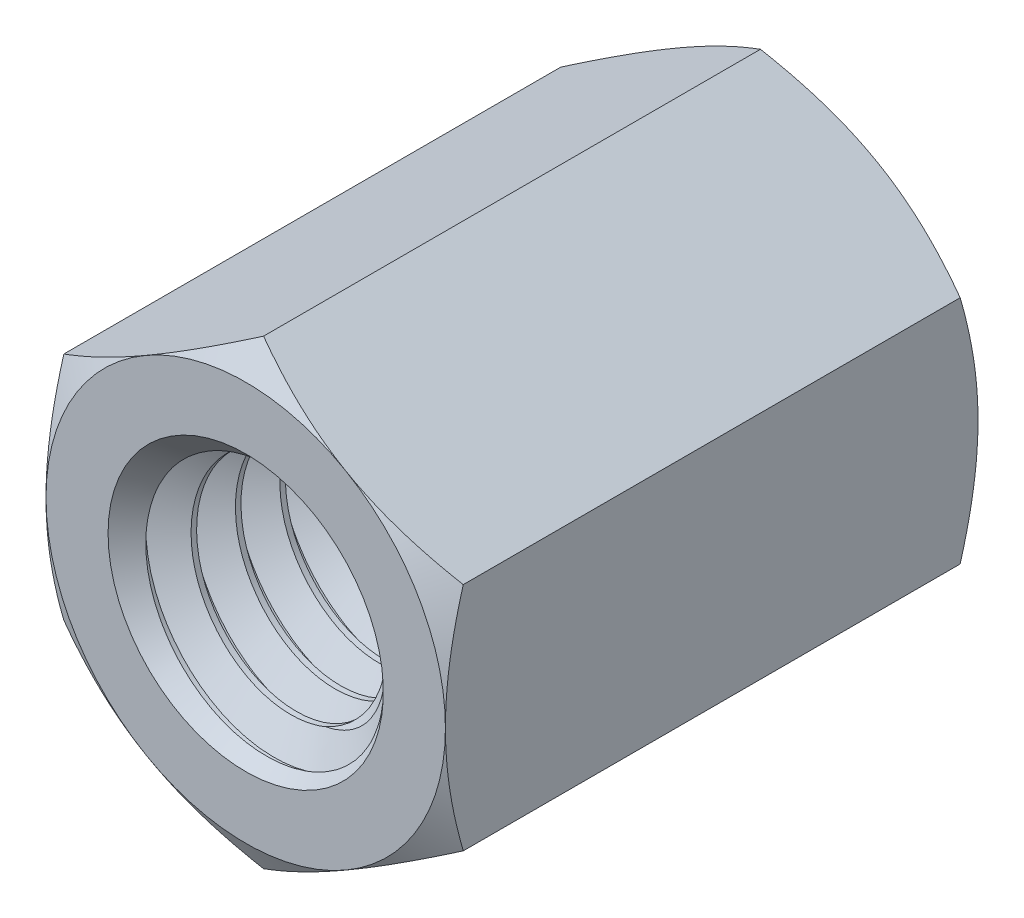
SolidWorks part; units mm, degrees
material "Brass"
ref_plane "Front Plane" through (0, 0, 0) normal (0, 0, 1) x (1, 0, 0)
ref_plane "Top Plane" through (0, 0, 0) normal (0, 1, 0) x (1, 0, 0)
ref_plane "Right Plane" through (0, 0, 0) normal (1, 0, 0) x (0, 0, -1)
sketch "Sketch3" plane through (0, 0, 0) normal (1, 0, 0) x (0, 0, -1)
  line L0 (-3, 0) -> (3, 0) construction
  line L1 (0, 2.25) -> (0, -2.25) construction
  line L2 (-3, 1.5) -> (-3, -1.5) construction
  point P2 (-1.8, 0)
  point P3 (1.8, 0)
  dimension "Length" = 6
  dimension "Min Thread Length" = 4.8
  dimension "D1" = 4.8
  dimension "Thread Dia" = 3
  dimension "Hex" = 4.5
sketch "Sketch1" plane through (0, 0, 0) normal (0, 0, 1) x (1, 0, 0)
  line L1 (0, 2.5981) -> (-2.25, 1.299)
  line L2 (-2.25, 1.299) -> (-2.25, -1.299)
  line L3 (-2.25, -1.299) -> (0, -2.5981)
  line L4 (0, -2.5981) -> (2.25, -1.299)
  line L5 (2.25, -1.299) -> (2.25, 1.299)
  line L6 (2.25, 1.299) -> (0, 2.5981)
  circle A0 centre (0, 0) radius 2.25 construction
  circle A1 centre (0, 0) radius 1.5
extrude "Extrude1" add sketch "Sketch1" along normal up to vertex (3 mm away) and the other way up to vertex (3 mm away) up to point (0, 0, 3) other way up to point (0, 0, -3)
sketch "Sketch11" plane through (0, 0, -3) normal (0, 0, -1) x (-1, 0, 0)
  circle A0 centre (0, 0) radius 1.5 construction
  circle A1 centre (0, 0) radius 1.5
curve "Helix/Spiral1" pitch 0.5 height 6.5 radius 1.5 centre (0, 0, -3) axis (0, 0, 1) start towards (0, 1, 0) parameters "Pitch"=0.5
sketch "Sketch12" plane through (0, 0, 0) normal (1, 0, 0) x (0, 0, -1)
  line L0 (3.4375, 1.5) -> (3, 1.5)
  line L1 (3.4375, 1.5) -> (3.25, 1.1752)
  line L2 (3.25, 1.1752) -> (3.1875, 1.1752)
  line L3 (3.1875, 1.1752) -> (3, 1.5)
  line L4 (3.2187, 1.1752) -> (3.2187, 1.5) construction
  line L5 (3.3437, 1.3376) -> (3.0937, 1.3376) construction
  dimension "D1" = 0.0625
  dimension "D2" = 0.25
  dimension "D3" = 60
sweep "Sweep1" add profiles "Sketch12" path "Helix/Spiral1"
sketch "Sketch6" plane through (0, 0, -3) normal (0, 0, -1) x (-1, 0, 0)
  line L6 (0, 2.5981) -> (-2.25, 1.299)
  line L7 (-2.25, 1.299) -> (-2.25, -1.299)
  line L8 (-2.25, -1.299) -> (0, -2.5981)
  line L9 (0, -2.5981) -> (2.25, -1.299)
  line L10 (2.25, -1.299) -> (2.25, 1.299)
  line L11 (2.25, 1.299) -> (0, 2.5981)
  line L12 (0, 2.5981) -> (-2.25, 1.299)
  line L13 (-2.25, 1.299) -> (-2.25, -1.299)
  line L14 (-2.25, -1.299) -> (0, -2.5981)
  line L15 (0, -2.5981) -> (2.25, -1.299)
  line L16 (2.25, -1.299) -> (2.25, 1.299)
  line L17 (2.25, 1.299) -> (0, 2.5981)
  dimension "D1" = 0
extrude "Extrude2" cut sketch "Sketch6" along normal through all
sketch "Sketch7" plane through (0, 0, -3) normal (0, 0, -1) x (-1, 0, 0)
  circle A2 centre (0, 0) radius 1.5508
  circle A3 centre (0, 0) radius 1.5508
  dimension "D1" = 0.0508
extrude "Extrude3" cut sketch "Sketch7" against normal through all draft 43
sketch "Sketch8" plane through (0, 0, -3) normal (0, 0, -1) x (-1, 0, 0)
  circle A0 centre (0, 0) radius 2.25 construction
  circle A1 centre (0, 0) radius 2.25
extrude "Extrude4" cut sketch "Sketch8" against normal through all draft 60 flip side to cut
mirror "Mirror1" about plane through (0, 0, 0) normal (0, 0, 1) of "Extrude2", "Extrude3", "Extrude4"
sketch "Sketch9" [suppressed] plane through (0, 0, 0) normal (1, 0, 0) x (0, 0, -1)
  line L1 (-1.2, 1.1353) -> (1.2, 1.1353)
  line L2 (-1.2, 1.1353) -> (-1.2, 0)
  line L3 (-1.2, 0) -> (1.2, 0)
  line L4 (1.2, 1.1353) -> (1.2, 0)
  line L7 (-6, 0) -> (6, 0) construction
revolve "Revolve" [suppressed] add sketch "Sketch9" angle 360 about L0
sketch "Sketch10" [suppressed] plane through (0, 0, 0) normal (1, 0, 0) x (0, 0, -1)
  line L0 (6, 1.25) -> (1.2, 1.25)
  line L1 (-6, 1.25) -> (-1.2, 1.25)
  line L2 (1.2, 1.25) -> (1.2, -1.25)
  line L3 (-6, -1.25) -> (-1.2, -1.25)
  line L4 (-1.2, 1.25) -> (-1.2, -1.25)
  line L5 (1.2, -1.25) -> (6, -1.25)
equation "\"D1@Sketch3\" = \"Min Thread Length@Sketch3\""
equation "\"D3@Helix/Spiral1\" = \"Length@Sketch3\"+\"Pitch@Helix/Spiral1\""
equation "\"D1@Sketch12\" = \"Pitch@Helix/Spiral1\"*.125"
equation "\"D2@Sketch12\" = \"Pitch@Helix/Spiral1\"*.5"
